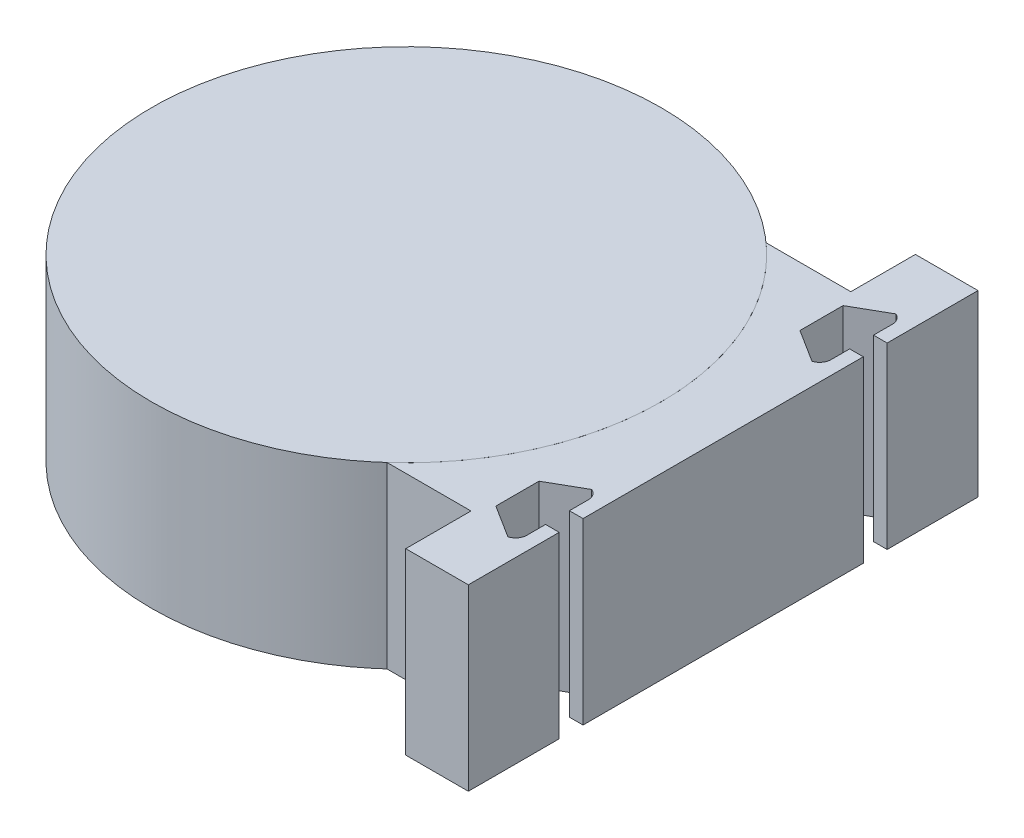
SolidWorks part; units mm, degrees
ref_plane "Front Plane" through (0, 0, 0) normal (0, 0, 1) x (1, 0, 0)
ref_plane "Top Plane" through (0, 0, 0) normal (0, 1, 0) x (1, 0, 0)
ref_plane "Right Plane" through (0, 0, 0) normal (1, 0, 0) x (0, 0, -1)
sketch "Sketch1" plane through (0, 0, 0) normal (0, 1, 0) x (1, 0, 0)
  circle A0 centre (0, 0) radius 28.5
  dimension "D1" = 57
extrude "Boss-Extrude1" add sketch "Sketch1" along normal blind 20
sketch "Sketch2" plane through (0, 20, 0) normal (0, 1, 0) x (1, 0, 0)
  line L4 (28.4332, 28.5) -> (28.4332, -28.5)
  line L5 (28.4332, 28.5) -> (35.4332, 28.5)
  line L6 (28.4332, -28.5) -> (35.4332, -28.5)
  line L7 (35.4332, 28.5) -> (35.4332, -28.5)
  line L8 (28.4332, 21.2771) -> (18.9615, 21.2771)
  line L9 (28.4332, 21.2771) -> (28.4332, -21.2005)
  line L10 (18.9615, 21.2771) -> (18.9615, -21.2005)
  line L11 (28.4332, -21.2005) -> (18.9615, -21.2005)
  circle A1 centre (0, 0) radius 28.5 construction
  circle M6 centre (0, 0) radius 28.5
  dimension "D1" = 7
extrude "Boss-Extrude3" add sketch "Sketch2" against normal blind 20 separate body contours L4 L8 M6 | L11 L4 M6 | L7 L5 L4 L6 M6 region at (31.9347, 20, 0) region at (25.685, 20, -16.2587) region at (25.7086, 20, 16.1991)
sketch "Sketch6" plane through (0, 0, 0) normal (0, -1, 0) x (1, 0, 0)
  line L0 (35.4332, 18.338) -> (33.9092, 18.338)
  line L1 (35.4332, -28.5) -> (35.4332, 28.5) construction
  line L2 (33.9092, 18.338) -> (33.9092, 21.64)
  line L3 (33.9092, 21.64) -> (32.999, 21.64)
  line L4 (32.999, 21.64) -> (29.3461, 19.3375)
  line L5 (29.3461, 19.3375) -> (29.3461, 14.5115)
  line L6 (29.3461, 14.5115) -> (33.095, 12.369)
  line L7 (33.095, 12.369) -> (33.9092, 12.369)
  line L8 (33.9092, 12.369) -> (33.9092, 15.671)
  line L9 (33.9092, 15.671) -> (35.4332, 15.671)
  line L10 (35.4332, 15.671) -> (35.4332, 18.338)
  line L11 (28.4332, 28.5) -> (35.4332, 28.5) construction
  point P5 (33.095, 27.5586)
  dimension "D1" = 1.524
  dimension "D2" = 3.302
  dimension "D3" = 2.667
  dimension "D4" = 3.302
  dimension "D5" = 4.318
  dimension "D6" = 4.318
  dimension "D7" = 4.826
  dimension "D8" = 0.9102
  dimension "D9" = 0.8142
  dimension "D10" = 6.86
sketch "Sketch8" plane through (0, 0, 0) normal (0, -1, 0) x (1, 0, 0)
  line L0 (35.4332, -15.671) -> (33.9092, -15.671)
  line L2 (33.9092, -15.671) -> (33.9092, -12.369)
  line L3 (33.9092, -12.369) -> (32.999, -12.369)
  line L4 (32.999, -12.369) -> (29.3461, -14.6715)
  line L5 (29.3461, -14.6715) -> (29.3461, -19.4975)
  line L6 (29.3461, -19.4975) -> (33.095, -21.64)
  line L7 (33.095, -21.64) -> (33.9092, -21.64)
  line L8 (33.9092, -21.64) -> (33.9092, -18.338)
  line L9 (33.9092, -18.338) -> (35.4332, -18.338)
  line L10 (35.4332, -18.338) -> (35.4332, -15.671)
  line L12 (35.4332, -28.5) -> (35.4332, 28.5) construction
  line L13 (28.4332, -28.5) -> (35.4332, -28.5) construction
  point P5 (33.9027, 12.0008)
  point P13 (33.5021, -21.64)
  dimension "D1" = 1.524
  dimension "D2" = 3.302
  dimension "D3" = 2.667
  dimension "D4" = 3.302
  dimension "D5" = 4.318
  dimension "D6" = 4.318
  dimension "D7" = 4.826
  dimension "D8" = 0.9102
  dimension "D9" = 0.8142
  dimension "D10" = 0
  dimension "D11" = 6.86
extrude "Cut-Extrude1" cut sketch "Sketch6" against normal through all both and the other way through all
extrude "Cut-Extrude2" cut sketch "Sketch8" against normal through all both
fillet "Fillet1" radius 1.27 4 edges at (33.9092, 10, -21.64) (33.9092, 10, -12.369) (33.9092, 10, 21.64) (33.9092, 10, 12.369)
